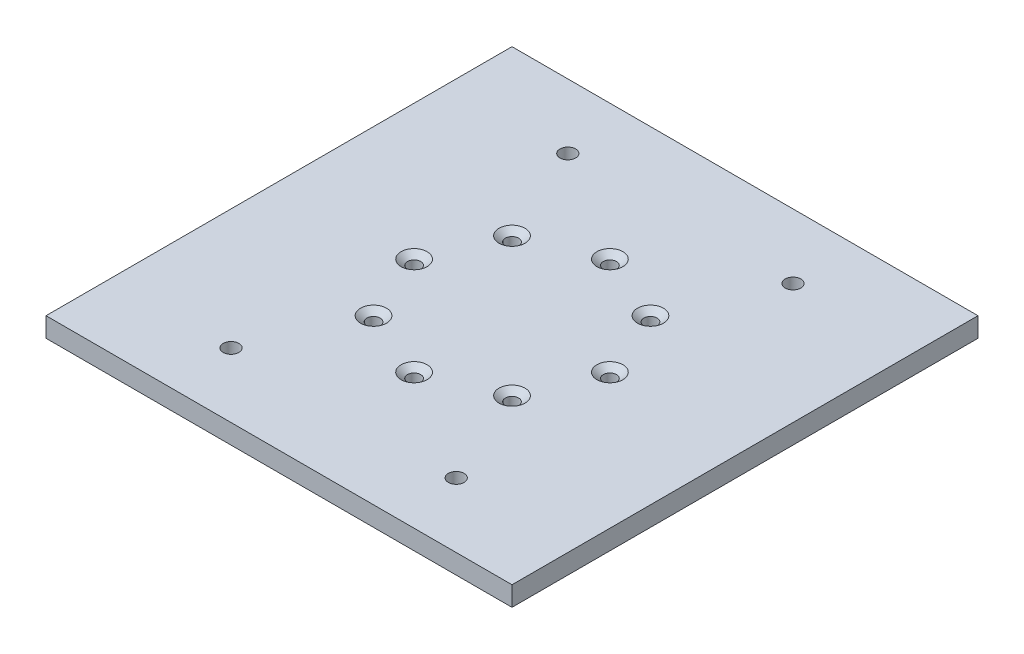
SolidWorks part; units mm, degrees
material "6061-T6 (SS)"
ref_plane "Front Plane" through (0, 0, 0) normal (0, 0, 1) x (1, 0, 0)
ref_plane "Top Plane" through (0, 0, 0) normal (0, 1, 0) x (1, 0, 0)
ref_plane "Right Plane" through (0, 0, 0) normal (1, 0, 0) x (0, 0, -1)
sketch "Sketch1" plane through (0, 0, 0) normal (0, 1, 0) x (1, 0, 0)
  line L1 (-75.565, -75.565) -> (75.565, -75.565)
  line L2 (-75.565, -75.565) -> (-75.565, 75.565)
  line L3 (-75.565, 75.565) -> (75.565, 75.565)
  line L4 (75.565, -75.565) -> (75.565, 75.565)
  line L10 (-75.565, 75.565) -> (0, 0) construction
  line L11 (-38.1, 73.025) -> (38.1, 73.025) construction
  line L12 (-38.1, 73.025) -> (-38.1, 47.625) construction
  line L13 (-38.1, 47.625) -> (38.1, 47.625) construction
  line L14 (38.1, 73.025) -> (38.1, 47.625) construction
  line L15 (-38.1, 73.025) -> (38.1, 47.625) construction
  line L16 (-38.1, 47.625) -> (38.1, 73.025) construction
  line L17 (-44.45, 75.565) -> (44.45, 75.565) construction
  line L18 (-44.45, 75.565) -> (-44.45, 45.085) construction
  line L19 (-44.45, 45.085) -> (44.45, 45.085) construction
  line L20 (44.45, 75.565) -> (44.45, 45.085) construction
  line L21 (-44.45, 75.565) -> (44.45, 45.085) construction
  line L22 (-44.45, 45.085) -> (44.45, 75.565) construction
  line L23 (0, 0) -> (75.565, 75.565) construction
  line L24 (0, 0) -> (-75.565, -75.565) construction
  line L25 (0, 0) -> (75.565, -75.565) construction
  circle A0 centre (0, 0) radius 38.1 construction
  circle A1 centre (0, 0) radius 41.275 construction
  point P0 (0, 0)
  point P1 (-75.565, 0)
  point P17 (0, 60.325)
  point P22 (0, 60.325)
  point P27 (-75.565, 0)
  point P28 (0, 75.565)
  dimension "D4" = 76.2
  dimension "D5" = 82.55
  dimension "D6" = 2.54
  dimension "D7" = 25.4
  dimension "D8" = 76.2
  dimension "D9" = 88.9
  dimension "D10" = 6.35
  dimension "D12" = 151.13
extrude "Boss-Extrude1" add sketch "Sketch1" along normal blind 6.35
hole_wizard "#7 (0.201) Diameter Hole1" positions "Sketch3" profile "Sketch2" hole size "#7" standard "ANSI Inch" end condition through all
sketch "Sketch3" plane through (0, 6.35, 0) normal (0, 1, 0) x (-1, 0, 0)
  line L0 (-36.5125, -54.61) -> (0, 0) construction
  line L1 (0, 0) -> (36.5125, -54.61) construction
  line L5 (-873.478, -47.625) -> (49126.522, -47.625) construction
  point P0 (36.5125, -54.61)
  point P1 (-36.5125, -54.61)
  dimension "D1" = 73.025
  dimension "D2" = 47.625
  dimension "D3" = 6.985
sketch "Sketch2" plane through (-36.5125, 6.35, -54.61) normal (1, 0, 0) x (0, 0, 1)
  line L0 (0, 0) -> (0, 6.35)
  line L1 (0, 6.35) -> (2.5527, 6.35)
  line L2 (2.5527, 6.35) -> (2.5527, 0)
  line L5 (2.5527, 0) -> (0, 0)
  line L11 (0, -6.35) -> (0, 107.95) construction
  dimension "Thru Hole Dia." = 5.1054
  dimension "Thru Hole Depth" = 6.35
ref_axis "Axis1" through (0, 0, 0) along (0, 1, 0)
pattern_circular "CirPattern1" count 2 over 360 about axis through (0, 0, 0) along (0, 1, 0) of "#7 (0.201) Diameter Hole1"
hole_wizard "CSK for #8 Flat Head Machine Screw (100)1" positions "Sketch5" profile "Sketch4" countersink size "#8" standard "Ansi Inch" end condition through all
sketch "Sketch5" plane through (0, 6.35, 0) normal (0, 1, 0) x (-1, 0, 0)
  point P0 (0, 31.75)
  dimension "D1" = 31.75
sketch "Sketch4" plane through (0, 6.35, 31.75) normal (1, 0, 0) x (0, 0, 1)
  line L0 (0, 0) -> (0, 6.35)
  line L1 (0, 6.35) -> (2.1526, 6.35)
  line L2 (2.1526, 6.35) -> (2.1526, 1.7317)
  line L3 (2.1526, 1.7317) -> (4.2164, 0)
  line L5 (4.2164, 0) -> (0, 0)
  line L6 (-2.1526, 1.7317) -> (-4.2164, 0) construction
  line L11 (0, -6.35) -> (0, 107.95) construction
  dimension "Thru Hole Dia." = 4.3053
  dimension "Thru Hole Depth" = 6.35
  dimension "Near C'Sink Dia." = 8.4328
  dimension "Near C'Sink Angle" = 100
pattern_circular "CirPattern2" count 8 over 360 about axis through (0, 0, 0) along (0, 1, 0) of "CSK for #8 Flat Head Machine Screw (100)1"
